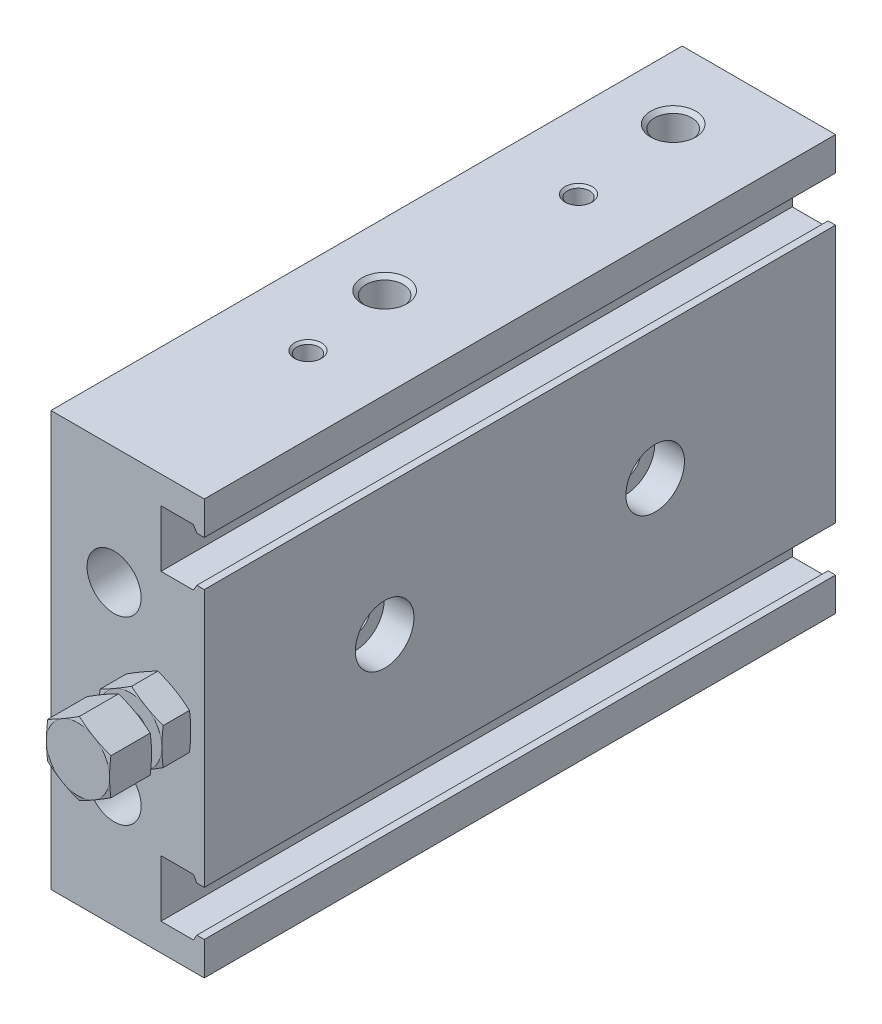
SolidWorks part; units mm, degrees
ref_plane "前视基准面" through (0, 0, 0) normal (0, 0, 1) x (1, 0, 0)
ref_plane "上视基准面" through (0, 0, 0) normal (0, 1, 0) x (1, 0, 0)
ref_plane "右视基准面" through (0, 0, 0) normal (1, 0, 0) x (0, 0, -1)
sketch "草图1" plane through (0, 0, 0) normal (0, 0, 1) x (1, 0, 0)
  line L0 (-7, 23) -> (-7, -23)
  line L1 (-7, -23) -> (10, -23)
  line L2 (10, -23) -> (10, -19.3)
  line L3 (10, -19.3) -> (9.1753, -19.3)
  line L4 (9.1753, -19.3) -> (8.8, -19.95)
  line L5 (8.8, -19.95) -> (5.2, -19.95)
  line L6 (5.2, -19.95) -> (5.2, -13.65)
  line L7 (5.2, -13.65) -> (8.8, -13.65)
  line L8 (8.8, -13.65) -> (9.1753, -14.3)
  line L9 (9.1753, -14.3) -> (10, -14.3)
  line L10 (10, -14.3) -> (10, 14.3)
  line L11 (10, 14.3) -> (9.1753, 14.3)
  line L12 (9.1753, 14.3) -> (8.8, 13.65)
  line L13 (8.8, 13.65) -> (5.2, 13.65)
  line L14 (5.2, 13.65) -> (5.2, 19.95)
  line L15 (5.2, 19.95) -> (8.8, 19.95)
  line L16 (8.8, 19.95) -> (9.1753, 19.3)
  line L17 (9.1753, 19.3) -> (10, 19.3)
  line L18 (10, 19.3) -> (10, 23)
  line L19 (10, 23) -> (-7, 23)
extrude "凸台-拉伸1" add sketch "草图1" against normal blind 70
sketch "草图2" plane through (0, 0, 0) normal (1, 0, 0) x (0, 0, -1)
  line L0 (0, 10) -> (0, 13)
  line L1 (0, 13) -> (20, 13)
  line L2 (20, 13) -> (20, 15)
  line L3 (20, 15) -> (40, 15)
  line L4 (40, 15) -> (40, 10)
  line L5 (40, 10) -> (0, 10)
  line L6 (40, 10) -> (0, 10) construction
revolve "切除-旋转1" cut sketch "草图2" angle 360 about L6 reverse direction yes
sketch "草图3" plane through (0, 0, 0) normal (1, 0, 0) x (0, 0, -1)
  line L0 (0, -10) -> (0, -7)
  line L1 (0, -7) -> (20, -7)
  line L2 (20, -7) -> (20, -5)
  line L3 (20, -5) -> (40, -5)
  line L4 (40, -5) -> (40, -10)
  line L5 (40, -10) -> (0, -10)
  line L6 (40, -10) -> (0, -10) construction
revolve "切除-旋转2" cut sketch "草图3" angle 360 about L6 reverse direction yes
ref_plane "基准面1" through (0, 0, -20) normal (0, 0, 1) x (1, 0, 0)
sketch "草图4" plane through (0, 0, -20) normal (0, 0, 1) x (1, 0, 0)
  line L0 (-7, 0) -> (-7, 1.7)
  line L1 (-7, 1.7) -> (6.7, 1.7)
  line L2 (6.7, 1.7) -> (6.7, 3.25)
  line L3 (6.7, 3.25) -> (10, 3.25)
  line L4 (10, 3.25) -> (10, 0)
  line L5 (10, 0) -> (-7, 0)
  line L6 (10, 0) -> (-7, 0) construction
revolve "切除-旋转3" cut sketch "草图4" angle 360 about L6 reverse direction yes
ref_plane "基准面2" through (0, 0, -50) normal (0, 0, 1) x (1, 0, 0)
sketch "草图5" plane through (0, 0, -50) normal (0, 0, 1) x (1, 0, 0)
  line L0 (-7, 0) -> (-7, 1.7)
  line L1 (-7, 1.7) -> (6.7, 1.7)
  line L2 (6.7, 1.7) -> (6.7, 3.25)
  line L3 (6.7, 3.25) -> (10, 3.25)
  line L4 (10, 3.25) -> (10, 0)
  line L5 (10, 0) -> (-7, 0)
  line L6 (10, 0) -> (-7, 0) construction
revolve "切除-旋转4" cut sketch "草图5" angle 360 about L6 reverse direction yes
ref_plane "基准面3" through (1.5, 0, 0) normal (1, 0, 0) x (0, 0, -1)
sketch "草图6" plane through (0, 0, -20) normal (0, 0, 1) x (1, 0, 0)
  line L0 (-7, 0) -> (-7, 2)
  line L1 (-7, 2) -> (-6.621, 1.621)
  line L2 (-6.621, 1.621) -> (0, 1.621)
  line L3 (0, 1.621) -> (0.9359, 0)
  line L4 (0.9359, 0) -> (-7, 0)
  line L5 (0.9359, 0) -> (-7, 0) construction
revolve "切除-旋转5" cut sketch "草图6" angle 360 about L5 reverse direction yes
sketch "草图7" plane through (0, 0, -50) normal (0, 0, 1) x (1, 0, 0)
  line L0 (-7, 0) -> (-7, 2)
  line L1 (-7, 2) -> (-6.621, 1.621)
  line L2 (-6.621, 1.621) -> (0, 1.621)
  line L3 (0, 1.621) -> (0.9359, 0)
  line L4 (0.9359, 0) -> (-7, 0)
  line L5 (0.9359, 0) -> (-7, 0) construction
revolve "切除-旋转6" cut sketch "草图7" angle 360 about L5 reverse direction yes
sketch "草图8" plane through (0, 0, 0) normal (1, 0, 0) x (0, 0, -1)
  line L0 (30, 17.3066) -> (27.933, 18.5)
  line L1 (27.933, 18.5) -> (27.933, 22.567)
  line L2 (27.933, 22.567) -> (27.5, 23)
  line L3 (27.5, 23) -> (30, 23)
  line L4 (30, 23) -> (30, 17.3066)
  line L5 (30, 23) -> (30, 17.3066) construction
revolve "切除-旋转7" cut sketch "草图8" angle 360 about L5 reverse direction yes
cosmetic thread "装饰螺纹线1" parameters "D1"=4.5, "D2"=5
sketch "草图9" plane through (0, 0, 0) normal (1, 0, 0) x (0, 0, -1)
  line L0 (62, 17.3066) -> (59.933, 18.5)
  line L1 (59.933, 18.5) -> (59.933, 22.567)
  line L2 (59.933, 22.567) -> (59.5, 23)
  line L3 (59.5, 23) -> (62, 23)
  line L4 (62, 23) -> (62, 17.3066)
  line L5 (62, 23) -> (62, 17.3066) construction
revolve "切除-旋转8" cut sketch "草图9" angle 360 about L5 reverse direction yes
cosmetic thread "装饰螺纹线2" parameters "D1"=4.5, "D2"=5
sketch "草图10" plane through (0, 0, 0) normal (1, 0, 0) x (0, 0, -1)
  line L0 (30, -23) -> (27.5, -23)
  line L1 (27.5, -23) -> (27.933, -22.567)
  line L2 (27.933, -22.567) -> (27.933, -18.5)
  line L3 (27.933, -18.5) -> (30, -17.3066)
  line L4 (30, -17.3066) -> (30, -23)
  line L5 (30, -17.3066) -> (30, -23) construction
revolve "切除-旋转9" cut sketch "草图10" angle 360 about L5 reverse direction yes
cosmetic thread "装饰螺纹线3" parameters "D1"=4.5, "D2"=5
sketch "草图11" plane through (0, 0, 0) normal (1, 0, 0) x (0, 0, -1)
  line L0 (62, -23) -> (59.5, -23)
  line L1 (59.5, -23) -> (59.933, -22.567)
  line L2 (59.933, -22.567) -> (59.933, -18.5)
  line L3 (59.933, -18.5) -> (62, -17.3066)
  line L4 (62, -17.3066) -> (62, -23)
  line L5 (62, -17.3066) -> (62, -23) construction
revolve "切除-旋转10" cut sketch "草图11" angle 360 about L5 reverse direction yes
cosmetic thread "装饰螺纹线4" parameters "D1"=4.5, "D2"=5
sketch "草图12" plane through (1.5, 0, 0) normal (1, 0, 0) x (0, 0, -1)
  line L0 (20, 17.7901) -> (18.7705, 18.5)
  line L1 (18.7705, 18.5) -> (18.7705, 22.7295)
  line L2 (18.7705, 22.7295) -> (18.5, 23)
  line L3 (18.5, 23) -> (20, 23)
  line L4 (20, 23) -> (20, 17.7901)
  line L5 (20, 23) -> (20, 17.7901) construction
revolve "切除-旋转11" cut sketch "草图12" angle 360 about L5 reverse direction yes
cosmetic thread "装饰螺纹线5" parameters "D1"=4.5, "D2"=3
sketch "草图13" plane through (1.5, 0, 0) normal (1, 0, 0) x (0, 0, -1)
  line L0 (50, 17.7901) -> (48.7705, 18.5)
  line L1 (48.7705, 18.5) -> (48.7705, 22.7295)
  line L2 (48.7705, 22.7295) -> (48.5, 23)
  line L3 (48.5, 23) -> (50, 23)
  line L4 (50, 23) -> (50, 17.7901)
  line L5 (50, 23) -> (50, 17.7901) construction
revolve "切除-旋转12" cut sketch "草图13" angle 360 about L5 reverse direction yes
cosmetic thread "装饰螺纹线6" parameters "D1"=4.5, "D2"=3
sketch "草图14" plane through (1.5, 0, 0) normal (1, 0, 0) x (0, 0, -1)
  line L0 (20, -23) -> (18.5, -23)
  line L1 (18.5, -23) -> (18.7705, -22.7295)
  line L2 (18.7705, -22.7295) -> (18.7705, -18.5)
  line L3 (18.7705, -18.5) -> (20, -17.7901)
  line L4 (20, -17.7901) -> (20, -23)
  line L5 (20, -17.7901) -> (20, -23) construction
revolve "切除-旋转13" cut sketch "草图14" angle 360 about L5 reverse direction yes
cosmetic thread "装饰螺纹线7" parameters "D1"=4.5, "D2"=3
sketch "草图15" plane through (1.5, 0, 0) normal (1, 0, 0) x (0, 0, -1)
  line L0 (50, -23) -> (48.5, -23)
  line L1 (48.5, -23) -> (48.7705, -22.7295)
  line L2 (48.7705, -22.7295) -> (48.7705, -18.5)
  line L3 (48.7705, -18.5) -> (50, -17.7901)
  line L4 (50, -17.7901) -> (50, -23)
  line L5 (50, -17.7901) -> (50, -23) construction
revolve "切除-旋转14" cut sketch "草图15" angle 360 about L5 reverse direction yes
cosmetic thread "装饰螺纹线8" parameters "D1"=4.5, "D2"=3
ref_plane "基准面4" through (0, 23, 0) normal (0, 1, 0) x (1, 0, 0)
ref_plane "基准面5" through (0, -23, 0) normal (0, 1, 0) x (1, 0, 0)
ref_plane "基准面6" through (5, 0, 0) normal (1, 0, 0) x (0, 0, -1)
sketch "草图16" plane through (5, 0, 0) normal (1, 0, 0) x (0, 0, -1)
  line L0 (-3.2, 0) -> (-3.2, 3.5)
  line L1 (-3.2, 3.5) -> (-2.2622, 7)
  line L2 (-2.2622, 7) -> (-0.9378, 7)
  line L3 (-0.9378, 7) -> (0, 3.5)
  line L4 (0, 3.5) -> (0, 0)
  line L5 (0, 0) -> (-3.2, 0)
  line L6 (0, 0) -> (-3.2, 0) construction
revolve "旋转1" add sketch "草图16" angle 360 about L6 reverse direction yes
sketch "草图17" plane through (5, 0, 0) normal (1, 0, 0) x (0, 0, -1)
  line L0 (-9, 0) -> (-9, 3.5)
  line L1 (-9, 3.5) -> (-8.0622, 7)
  line L2 (-8.0622, 7) -> (-5.2878, 7)
  line L3 (-5.2878, 7) -> (-4.35, 3.5)
  line L4 (-4.35, 3.5) -> (-4.35, 2)
  line L5 (-4.35, 2) -> (-3.2, 2)
  line L6 (-3.2, 2) -> (-3.2, 0)
  line L7 (-3.2, 0) -> (-9, 0)
  line L8 (-3.2, 0) -> (-9, 0) construction
revolve "旋转2" add sketch "草图17" angle 360 about L8 reverse direction yes
sketch "草图18" plane through (0, 0, 0) normal (0, 0, 1) x (1, 0, 0)
  line L0 (1.5, 2.0207) -> (1.5, -2.0207)
  line L1 (1.5, -2.0207) -> (5, -4.0415)
  line L2 (5, -4.0415) -> (8.5, -2.0207)
  line L3 (8.5, -2.0207) -> (8.5, 2.0207)
  line L4 (8.5, 2.0207) -> (5, 4.0415)
  line L5 (5, 4.0415) -> (1.5, 2.0207)
  circle A0 centre (5, 0) radius 8
extrude "切除-拉伸1" cut sketch "草图18" along normal blind 9
ref_plane "基准面7" through (0, 0, -70) normal (0, 0, 1) x (1, 0, 0)
ref_plane "body_sw1 XY" through (0, 0, 0) normal (0, 0, -1) x (-1, 0, 0)
ref_plane "body_sw1 XZ" through (0, -16.8, 0) normal (0, 1, 0) x (1, 0, 0)
ref_plane "body_sw1 YZ" through (5.2, 0, 0) normal (1, 0, 0) x (0, 0, -1)
ref_axis "body_sw1 X" through (-80.9, -16.8, 0) along (1, 0, 0)
ref_axis "body_sw1 Y" through (5.2, 50, 0) along (0, -1, 0)
ref_axis "body_sw1 Z" through (5.2, -16.8, -80.9) along (0, 0, 1)
sketch3d "body_sw1"
  point P0 (5.2, -16.8, 0)
ref_plane "body_dummy XY" through (0, 0, 0) normal (0, 0, 1) x (1, 0, 0)
ref_plane "body_dummy XZ" through (0, 0, 0) normal (0, -1, 0) x (-1, 0, 0)
ref_plane "body_dummy YZ" through (0, 0, 0) normal (1, 0, 0) x (0, 0, -1)
ref_axis "body_dummy X" through (-80.9, 0, 0) along (1, 0, 0)
ref_axis "body_dummy Y" through (0, -50, 0) along (0, 1, 0)
ref_axis "body_dummy Z" through (0, 0, 80.9) along (0, 0, -1)
sketch3d "body_dummy"
  point P0 (0, 0, 0)
ref_plane "body_sw2 XY" through (0, 0, -70) normal (0, 0, -1) x (-1, 0, 0)
ref_plane "body_sw2 XZ" through (0, 16.8, 0) normal (0, 1, 0) x (1, 0, 0)
ref_plane "body_sw2 YZ" through (5.2, 0, 0) normal (1, 0, 0) x (0, 0, -1)
ref_axis "body_sw2 X" through (-80.9, 16.8, -70) along (1, 0, 0)
ref_axis "body_sw2 Y" through (5.2, 50, -70) along (0, -1, 0)
ref_axis "body_sw2 Z" through (5.2, 16.8, -80.9) along (0, 0, 1)
sketch3d "body_sw2"
  point P0 (5.2, 16.8, -70)
